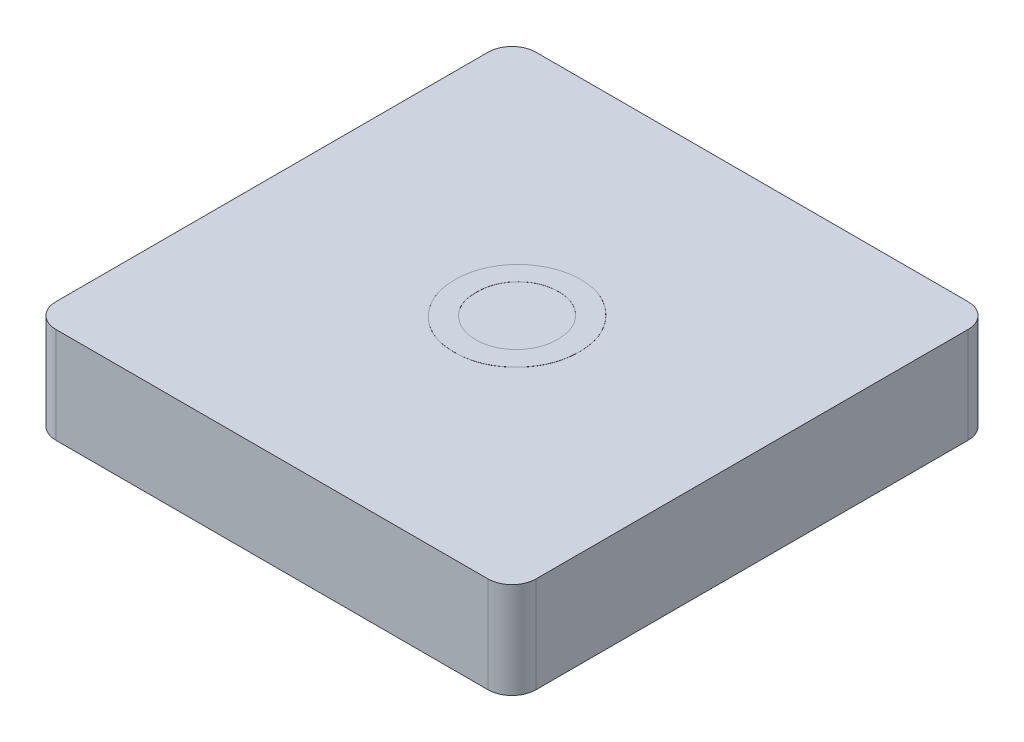
SolidWorks part; units mm, degrees
ref_plane "Front Plane" through (0, 0, 0) normal (0, 0, 1) x (1, 0, 0)
ref_plane "Top Plane" through (0, 0, 0) normal (0, 1, 0) x (1, 0, 0)
ref_plane "Right Plane" through (0, 0, 0) normal (1, 0, 0) x (0, 0, -1)
sketch "Sketch1" plane through (0, 0, 0) normal (0, 1, 0) x (1, 0, 0)
  line L0 (0, 0) -> (12.7, 0)
  line L1 (12.7, 0) -> (12.7, 12.7)
  line L2 (12.7, 12.7) -> (0, 12.7)
  line L3 (0, 12.7) -> (0, 0)
  dimension "D1" = 12.7
  dimension "D2" = 12.7
extrude "Boss-Extrude1" add sketch "Sketch1" along normal blind 2.54
fillet "Fillet1" radius 0.635 4 edges at (0, 1.27, -12.7) (12.7, 1.27, -12.7) (12.7, 1.27, 0) (0, 1.27, 0)
shell "Shell1" thickness 0.635 removed face at (6.35, 0, -6.35)
sketch "Sketch2" plane through (0, 1.905, 0) normal (0, -1, 0) x (-1, 0, 0)
  line L0 (-0.635, 6.35) -> (-12.065, 6.35) construction
  line L1 (-0.635, 12.065) -> (-0.635, 0.635) construction
  line L2 (-12.065, 0.635) -> (-12.065, 12.065) construction
  line L3 (-6.35, 0.635) -> (-6.35, 12.065) construction
  line L4 (-0.635, 0.635) -> (-12.065, 0.635) construction
  line L5 (-12.065, 12.065) -> (-0.635, 12.065) construction
  circle A0 centre (-6.35, 6.35) radius 2.54
  dimension "D1" = 5.08
extrude "Boss-Extrude2" add sketch "Sketch2" along normal up to surface (1.905 mm away) up to face at (6.35, 0, -6.35)
sketch "Sketch3" plane through (0, 2.54, 0) normal (0, 1, 0) x (1, 0, 0)
  line L0 (0, 12.065) -> (0, 0.635) construction
  line L1 (0.635, 0) -> (12.065, 0) construction
  text T0 "<b>O</b>"
  point P1 (0, 0)
  dimension "D1" = 4.572
  dimension "D2" = 4.826
extrude "Boss-Extrude3" add sketch "Sketch3" along normal blind 0.0025
